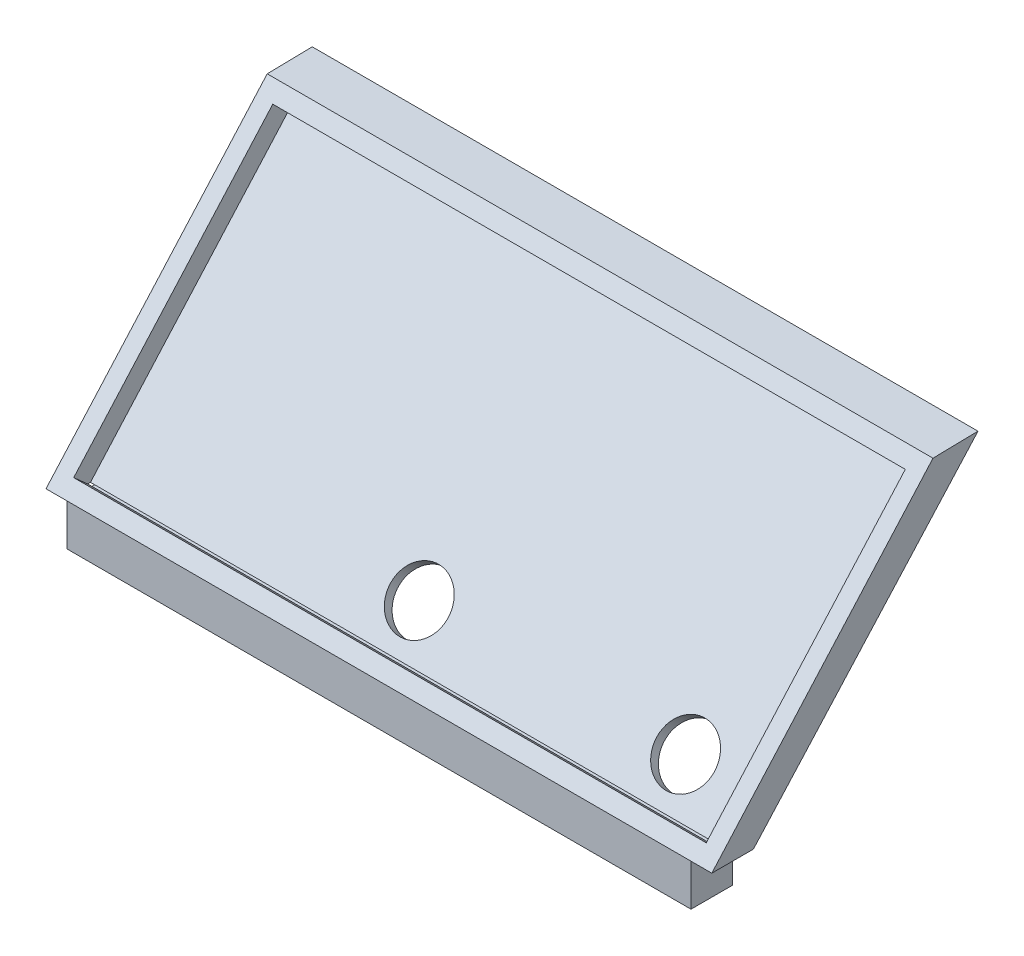
SolidWorks part; units mm, degrees
ref_plane "Front Plane" through (0, 0, 0) normal (0, 0, 1) x (1, 0, 0)
ref_plane "Top Plane" through (0, 0, 0) normal (0, 1, 0) x (1, 0, 0)
ref_plane "Right Plane" through (0, 0, 0) normal (1, 0, 0) x (0, 0, -1)
sketch "Sketch1" plane through (0, 0, 0) normal (0, 0, 1) x (1, 0, 0)
  line L1 (50.8, -25.4) -> (-50.8, -25.4)
  line L2 (50.8, -25.4) -> (50.8, 25.4)
  line L3 (50.8, 25.4) -> (-50.8, 25.4)
  line L4 (-50.8, -25.4) -> (-50.8, 25.4)
  line L5 (50.8, -25.4) -> (-50.8, 25.4) construction
  line L6 (50.8, 25.4) -> (-50.8, -25.4) construction
  point P0 (0, 0)
  dimension "D1" = 101.6
  dimension "D2" = 50.8
extrude "Boss-Extrude1" add sketch "Sketch1" against normal blind 228.6
sketch "Sketch2" plane through (0, 25.4, 0) normal (0, 1, 0) x (1, 0, 0)
  line L0 (0, 0) -> (0, 228.6) construction
  line L1 (50.8, 228.6) -> (-50.8, 228.6) construction
  line L3 (48.26, 200.66) -> (-48.26, 200.66)
  line L4 (48.26, 200.66) -> (48.26, 27.94)
  line L5 (48.26, 27.94) -> (-48.26, 27.94)
  line L6 (-48.26, 200.66) -> (-48.26, 27.94)
  line L7 (48.26, 200.66) -> (-48.26, 27.94) construction
  line L8 (48.26, 27.94) -> (-48.26, 200.66) construction
  point P6 (0, 114.3)
  dimension "D1" = 172.72
  dimension "D2" = 96.52
extrude "Cut-Extrude1" cut sketch "Sketch2" against normal blind 50.8
sketch "Sketch3" plane through (0, 25.4, 0) normal (0, 1, 0) x (1, 0, 0)
  line L0 (0, 0) -> (0, 76.1763)
  line L1 (-48.26, 200.66) -> (-48.26, 27.94) construction
  line L2 (48.26, 79.3513) -> (-48.26, 79.3513)
  line L3 (48.26, 79.3513) -> (48.26, 73.0013)
  line L4 (48.26, 73.0013) -> (-48.26, 73.0013)
  line L5 (-48.26, 79.3513) -> (-48.26, 73.0013)
  line L6 (48.26, 79.3513) -> (-48.26, 73.0013) construction
  line L7 (48.26, 73.0013) -> (-48.26, 79.3513) construction
  line M2 (-48.26, 27.94) -> (-48.26, 200.66)
  line M4 (48.26, 200.66) -> (48.26, 27.94)
  dimension "D1" = 6.35
extrude "Boss-Extrude2" add sketch "Sketch3" against normal blind 50.8 contours L4 L2 M4 M2 region at (47.2927, 25.4, -76.1763)
sketch "Sketch5" plane through (0, 25.4, 0) normal (0, 1, 0) x (1, 0, 0)
  line L0 (48.26, 73.0013) -> (50.8, 73.0013) construction
  line L3 (50.8, 228.6) -> (50.8, 0) construction
sketch "Sketch6" plane through (50.8, 0, 0) normal (1, 0, 0) x (0, 0, -1)
  line L0 (73.0013, 25.4) -> (106.7566, 63.3634)
  dimension "D1" = 50.8
sketch "Sketch7" plane through (0, 25.4, 0) normal (0, 1, 0) x (1, 0, 0)
  line L0 (48.26, 79.3513) -> (50.8, 79.3513)
  line L1 (50.8, 73.0013) -> (50.8, 106.7566) construction
sketch "Sketch8" plane through (50.8, 0, 0) normal (1, 0, 0) x (0, 0, -1)
  line L0 (79.3513, 25.4) -> (113.6226, 63.5)
  line L2 (106.7566, 63.3634) -> (113.6226, 63.5)
  dimension "D1" = 38.1
sketch "Sketch9" plane through (50.8, 0, 0) normal (1, 0, 0) x (0, 0, -1)
  line L0 (73.0013, 25.4) -> (79.3513, 25.4)
sketch "Sketch10" plane through (0, 25.4, 0) normal (0, 1, 0) x (1, 0, 0)
  line L0 (-48.26, 79.3513) -> (-50.8, 79.3513)
  line L1 (-50.8, 228.6) -> (-50.8, 0) construction
  line L2 (-48.26, 73.0013) -> (-50.8, 73.0013)
sketch "Sketch11" plane through (-50.8, 0, 0) normal (-1, 0, 0) x (0, 0, 1)
  line L0 (-79.3513, 25.4) -> (-113.6226, 63.5)
  line L1 (-73.0013, 25.4) -> (-106.7566, 63.3634)
  line L2 (-106.7566, 63.3634) -> (-113.6226, 63.5)
  line L3 (-79.3513, 25.4) -> (-73.0013, 25.4)
extrude "Boss-Extrude3" add sketch "Sketch11" against normal up to vertex (101.6 mm away) contours L1 L2 L0 L3 up to point (50.8, 63.3634, -106.7566)
sketch "Sketch13" plane through (0, 25.4, 0) normal (0, 1, 0) x (1, 0, 0)
  line L1 (-48.26, 200.66) -> (48.26, 200.66)
  line L2 (-48.26, 200.66) -> (-48.26, 226.06)
  line L3 (-48.26, 226.06) -> (48.26, 226.06)
  line L4 (48.26, 200.66) -> (48.26, 226.06)
  dimension "D1" = 25.4
extrude "Cut-Extrude2" cut sketch "Sketch13" against normal blind 50.8
sketch "Sketch14" plane through (0, 25.4, 0) normal (0, 1, 0) x (1, 0, 0)
  line L1 (-48.26, 27.94) -> (48.26, 27.94)
  line L2 (-48.26, 27.94) -> (-48.26, 2.54)
  line L3 (-48.26, 2.54) -> (48.26, 2.54)
  line L4 (48.26, 27.94) -> (48.26, 2.54)
  dimension "D1" = 96.52
  dimension "D2" = 25.4
extrude "Cut-Extrude3" cut sketch "Sketch14" against normal blind 50.8
sketch "Sketch15" plane through (0, 0, -73.0013) normal (0, 0, 1) x (1, 0, 0)
  line L1 (48.26, -25.4) -> (-48.26, -25.4)
  line L2 (48.26, -25.4) -> (48.26, 25.4)
  line L3 (48.26, 25.4) -> (-48.26, 25.4)
  line L4 (-48.26, -25.4) -> (-48.26, 25.4)
  line L5 (48.26, -25.4) -> (-48.26, 25.4) construction
  line L6 (48.26, 25.4) -> (-48.26, -25.4) construction
  point P0 (0, 0)
  dimension "D1" = 96.52
  dimension "D2" = 50.8
extrude "Cut-Extrude6" cut sketch "Sketch15" against normal blind 6.35
sketch "Sketch16" plane through (0, -25.0354, -28.1564) normal (0, 0.6645, 0.7473) x (1, 0, 0)
  line L0 (0, 67.4892) -> (0, 118.2892) construction
  line L1 (48.26, 67.4892) -> (-48.26, 67.4892) construction
  line L2 (50.8, 118.2892) -> (-50.8, 118.2892) construction
  line L4 (48.26, 70.0292) -> (-48.26, 70.0292)
  line L5 (48.26, 70.0292) -> (48.26, 115.7492)
  line L6 (48.26, 115.7492) -> (-48.26, 115.7492)
  line L7 (-48.26, 70.0292) -> (-48.26, 115.7492)
  line L8 (48.26, 70.0292) -> (-48.26, 115.7492) construction
  line L9 (48.26, 115.7492) -> (-48.26, 70.0292) construction
  point P7 (0, 92.8892)
  dimension "D1" = 96.52
  dimension "D2" = 45.72
extrude "Cut-Extrude7" cut sketch "Sketch16" against normal blind 3.175
sketch "Sketch17" plane through (0, 0, 0) normal (0, 0, 1) x (1, 0, 0)
  line L0 (50.8, 0) -> (-50.8, 0)
  line L1 (-50.8, 25.4) -> (-50.8, -25.4) construction
  line L4 (-50.8, 0) -> (-50.8, -25.4)
  line L5 (-50.8, -25.4) -> (50.8, -25.4)
  line L6 (50.8, 0) -> (50.8, -25.4)
  point P6 (0, 0)
extrude "Cut-Extrude8" cut sketch "Sketch17" against normal blind 228.6
sketch "Sketch20" plane through (-50.8, 0, 0) normal (-1, 0, 0) x (0, 0, 1)
  line L0 (-228.6, 0) -> (-177.8, 0)
  line L1 (-228.6, 0) -> (0, 0) construction
  line L3 (-177.8, 0) -> (-171.45, 0)
  line L4 (-177.8, 0) -> (-177.8, 12.7)
  line L5 (-177.8, 12.7) -> (-171.45, 12.7)
  line L6 (-171.45, 0) -> (-171.45, 12.7)
  line M4 (-228.6, 0) -> (0, 0)
  dimension "D1" = 50.8
  dimension "D2" = 6.35
  dimension "D3" = 12.7
extrude "Boss-Extrude5" add sketch "Sketch20" against normal blind 101.6 contours L6 L5 L4 M4 region at (-50.8, 6.35, -174.625)
sketch "Sketch24" plane through (0, 0, 0) normal (0, -1, 0) x (1, 0, 0)
  line L0 (48.26, -79.3513) -> (-48.26, -79.3513) construction
  line L1 (50.8, -73.0013) -> (38.1, -73.0013)
  line L2 (50.8, -73.0013) -> (50.8, -79.3513)
  line L3 (50.8, -79.3513) -> (38.1, -79.3513)
  line L4 (38.1, -73.0013) -> (38.1, -79.3513)
  dimension "D1" = 12.7
extrude "Boss-Extrude8" add sketch "Sketch24" along normal blind 19.05
sketch "Sketch26" plane through (0, 0, 0) normal (0, -1, 0) x (1, 0, 0)
  line L0 (-50.8, -228.6) -> (-50.8, 0) construction
  line L1 (-50.8, -171.45) -> (-38.1, -171.45)
  line L2 (-50.8, -171.45) -> (-50.8, -177.8)
  line L3 (-50.8, -177.8) -> (-38.1, -177.8)
  line L4 (-38.1, -171.45) -> (-38.1, -177.8)
  line L5 (48.26, -177.8) -> (-48.26, -177.8) construction
  dimension "D1" = 12.7
extrude "Boss-Extrude10" add sketch "Sketch26" along normal blind 19.05
sketch "Sketch27" plane through (0, 0, 0) normal (0, -1, 0) x (1, 0, 0)
  line L0 (50.8, -228.6) -> (50.8, -79.3513) construction
  line L1 (50.8, -177.8) -> (38.1, -177.8)
  line L2 (50.8, -177.8) -> (50.8, -171.45)
  line L3 (50.8, -171.45) -> (38.1, -171.45)
  line L4 (38.1, -177.8) -> (38.1, -171.45)
  line L5 (48.26, -171.45) -> (-38.1, -171.45) construction
  dimension "D1" = 12.7
extrude "Boss-Extrude11" add sketch "Sketch27" along normal blind 19.05
sketch "Sketch33" plane through (0, 0, -2.54) normal (0, 0, -1) x (-1, 0, 0)
  line L1 (48.26, 0) -> (48.26, 25.4) construction
  line L2 (48.26, 12.7) -> (-48.26, 12.7) construction
  line L3 (-48.26, 0) -> (-48.26, 25.4) construction
  line L5 (48.26, 13.97) -> (-48.26, 13.97)
  line L6 (48.26, 13.97) -> (48.26, 11.43)
  line L7 (48.26, 11.43) -> (-48.26, 11.43)
  line L8 (-48.26, 13.97) -> (-48.26, 11.43)
  line L9 (48.26, 13.97) -> (-48.26, 11.43) construction
  line L10 (48.26, 11.43) -> (-48.26, 13.97) construction
  point P6 (0, 12.7)
  dimension "D1" = 2.54
extrude "Boss-Extrude13" add sketch "Sketch33" along normal blind 2.54
sketch "Sketch34" plane through (0, 0, -226.06) normal (0, 0, 1) x (1, 0, 0)
  line L0 (0, 0) -> (0, 25.4) construction
  line L1 (-48.26, 0) -> (-48.26, 25.4) construction
  line L2 (48.26, 12.7) -> (-48.26, 12.7) construction
  line L3 (48.26, 0) -> (48.26, 25.4) construction
  line L4 (-48.26, 0) -> (48.26, 0) construction
  line L5 (48.26, 25.4) -> (-48.26, 25.4) construction
  line L7 (48.26, 13.97) -> (-48.26, 13.97)
  line L8 (48.26, 13.97) -> (48.26, 11.43)
  line L9 (48.26, 11.43) -> (-48.26, 11.43)
  line L10 (-48.26, 13.97) -> (-48.26, 11.43)
  line L11 (48.26, 13.97) -> (-48.26, 11.43) construction
  line L12 (48.26, 11.43) -> (-48.26, 13.97) construction
  point P12 (0, 12.7)
  dimension "D1" = 2.54
extrude "Boss-Extrude17" add sketch "Sketch34" along normal blind 2.54
sketch "Sketch36" plane through (-48.26, 0, 0) normal (1, 0, 0) x (0, 0, -1)
  line L0 (5.08, 11.43) -> (5.08, 13.97) construction
  line L1 (5.08, 13.97) -> (223.52, 13.97)
  line L2 (5.08, 13.97) -> (5.08, 11.43)
  line L3 (5.08, 11.43) -> (223.52, 11.43)
  line L4 (223.52, 13.97) -> (223.52, 11.43)
extrude "Boss-Extrude18" add sketch "Sketch36" along normal blind 2.54
sketch "Sketch37" plane through (48.26, 0, 0) normal (-1, 0, 0) x (0, 0, 1)
  line L1 (-5.08, 13.97) -> (-223.52, 13.97)
  line L2 (-5.08, 13.97) -> (-5.08, 11.43)
  line L3 (-5.08, 11.43) -> (-223.52, 11.43)
  line L4 (-223.52, 13.97) -> (-223.52, 11.43)
extrude "Boss-Extrude19" add sketch "Sketch37" along normal blind 2.54
sketch "Sketch45" plane through (0, 0, 0) normal (0, 0, 1) x (1, 0, 0)
  line L0 (-50.8, 12.7) -> (50.8, 12.7) construction
  line L1 (-50.8, 25.4) -> (-50.8, 0) construction
  line L2 (50.8, 0) -> (50.8, 25.4) construction
  line L3 (0, 0) -> (0, 25.4) construction
  line L4 (48.26, 25.4) -> (-48.26, 25.4) construction
  line L5 (0, 12.7) -> (-50.8, 12.7) construction
  line L6 (-25.0661, 12.7) -> (-50.8, 12.7) construction
  line L7 (44.537, 17.78) -> (44.537, 7.62)
  line L8 (-31.329, 17.78) -> (-44.537, 17.78)
  line L9 (-31.329, 17.78) -> (-31.329, 7.62)
  line L10 (-31.329, 7.62) -> (-44.537, 7.62)
  line L11 (-44.537, 17.78) -> (-44.537, 7.62)
  line L12 (-31.329, 17.78) -> (-44.537, 7.62) construction
  line L13 (-31.329, 7.62) -> (-44.537, 17.78) construction
  line L14 (31.329, 7.62) -> (44.537, 7.62)
  line L15 (31.329, 17.78) -> (31.329, 7.62)
  line L16 (31.329, 17.78) -> (44.537, 17.78)
  point P13 (-37.933, 12.7)
  dimension "D1" = 13.208
  dimension "D2" = 10.16
extrude "Cut-Extrude19" cut sketch "Sketch45" against normal blind 6.35
sketch "Sketch59" plane through (-50.8, 0, 0) normal (-1, 0, 0) x (0, 0, 1)
  line L0 (-79.3513, 25.4) -> (-73.0013, 25.4)
extrude "Cut-Extrude22" cut sketch "Sketch59" against normal blind 101.6 and the other way through all flip side to cut
sketch "Sketch60" plane through (0, -27.1451, -30.5291) normal (0, 0.6645, 0.7473) x (1, 0, 0)
  line L0 (44.85, 67.4892) -> (44.85, 77.0142) construction
  line L1 (50.8, 67.4892) -> (-50.8, 67.4892) construction
  line L2 (50.8, 77.0142) -> (38.1, 77.0142) construction
  line L3 (50.8, 67.4892) -> (50.8, 118.2892) construction
  circle A0 centre (38.1, 77.0142) radius 4.445
  dimension "D3" = 8.89
  dimension "D1" = 9.525
  dimension "D2" = 12.7
extrude "Cut-Extrude23" cut sketch "Sketch60" against normal blind 2.54
sketch "Sketch61" plane through (0, -27.1451, -30.5291) normal (0, 0.6645, 0.7473) x (1, 0, 0)
  line L0 (-23.2413, 67.4892) -> (-23.2413, 77.0142) construction
  line L1 (50.8, 67.4892) -> (-50.8, 67.4892) construction
  line L2 (-50.8, 77.0142) -> (-2.54, 77.0142) construction
  line L3 (-50.8, 67.4892) -> (-50.8, 118.2892) construction
  circle A0 centre (-2.54, 77.0142) radius 4.445
  dimension "D3" = 8.89
  dimension "D1" = 9.525
  dimension "D2" = 48.26
extrude "Cut-Extrude24" cut sketch "Sketch61" against normal blind 2.54
sketch "Sketch64" plane through (0, 25.4, 0) normal (0, -1, 0) x (-1, 0, 0)
  line L0 (0, 73.0013) -> (0, 79.3513) construction
  line L1 (-50.8, 73.0013) -> (50.8, 73.0013) construction
  line L2 (-50.8, 79.3513) -> (50.8, 79.3513) construction
  line L4 (-47.625, 73.0013) -> (47.625, 73.0013)
  line L5 (-47.625, 73.0013) -> (-47.625, 79.3513)
  line L6 (-47.625, 79.3513) -> (47.625, 79.3513)
  line L7 (47.625, 73.0013) -> (47.625, 79.3513)
  line L8 (-47.625, 73.0013) -> (47.625, 79.3513) construction
  line L9 (-47.625, 79.3513) -> (47.625, 73.0013) construction
  point P6 (0, 76.1763)
  dimension "D1" = 95.25
extrude "Boss-Extrude33" add sketch "Sketch64" along normal blind 6.35
